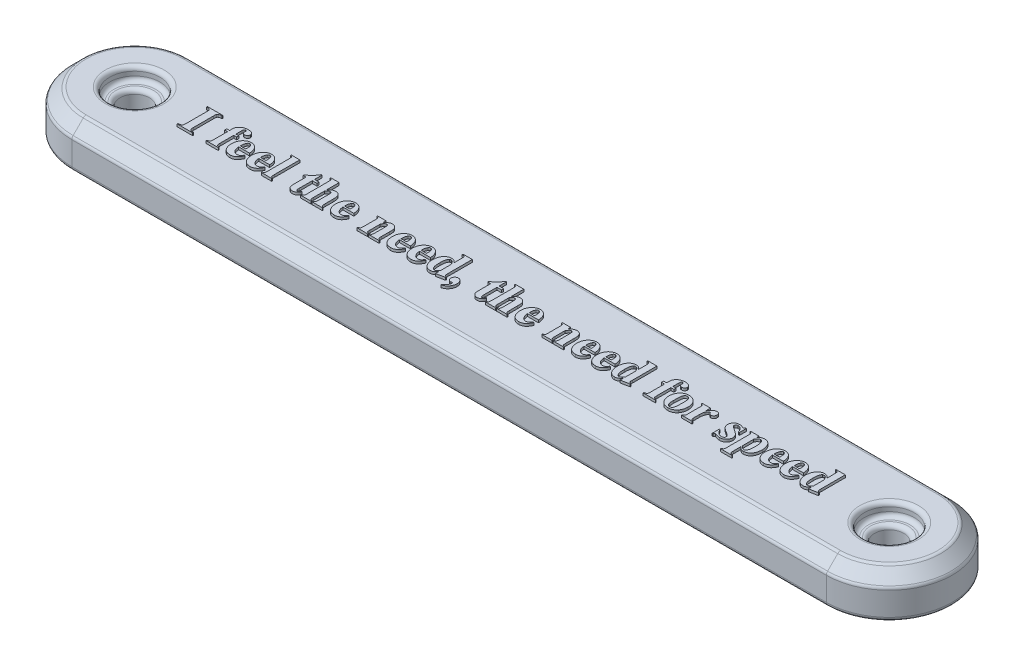
SolidWorks part; units mm, degrees
ref_plane "前视基准面" through (0, 0, 0) normal (0, 0, 1) x (1, 0, 0)
ref_plane "上视基准面" through (0, 0, 0) normal (0, 1, 0) x (1, 0, 0)
ref_plane "右视基准面" through (0, 0, 0) normal (1, 0, 0) x (0, 0, -1)
sketch "草图1" plane through (0, 0, 0) normal (0, 1, 0) x (1, 0, 0)
  line L4 (54.3761, 7.5) -> (144.3761, 7.5)
  line L6 (54.3761, -7.5) -> (144.3761, -7.5)
  circle A0 centre (54.3761, 0) radius 1.75
  circle A1 centre (144.3761, 0) radius 1.75
  arc A4 (144.3761, -7.5) -> (144.3761, 7.5) centre (144.3761, 0) ccw
  arc A5 (54.3761, 7.5) -> (54.3761, -7.5) centre (54.3761, 0) ccw
extrude "凸台-拉伸1" add sketch "草图1" along normal blind 5
chamfer "倒角1" distance 1.5 angle 45 4 edges at (99.3761, 5, -7.5) (46.8761, 5, 0) (151.8761, 5, 0) (99.3761, 5, 7.5)
sketch "草图2" plane through (0, 5, 0) normal (0, 1, 0) x (1, 0, 0)
  circle A0 centre (54.3761, 0) radius 3
  circle A1 centre (144.3761, 0) radius 3
extrude "切除-拉伸1" cut sketch "草图2" against normal blind 1.5
fillet "圆角1" radius 0.5 18 edges at (46.8761, 0, 0) (99.3761, 0, -7.5) (151.8761, 0, 0) (151.8761, 3.5, 0) (99.3761, 3.5, -7.5) (46.8761, 3.5, 0) (144.3761, 3.5, 3) (144.3761, 3.5, 1.75) (54.3761, 3.5, 3) (54.3761, 3.5, 1.75) (99.3761, 5, 6) (48.3761, 5, 0) (99.3761, 5, -6) (150.3761, 5, 0) (144.3761, 5, 3) (54.3761, 5, 3) (99.3761, 0, 7.5) (99.3761, 3.5, 7.5)
sketch "草图3" plane through (0, 5, 0) normal (0, 1, 0) x (1, 0, 0)
  text T0 "I feel the need, the need for speed" font "Times New Roman" height in points 14
extrude "凸台-拉伸2" add sketch "草图3" along normal blind 0.3
